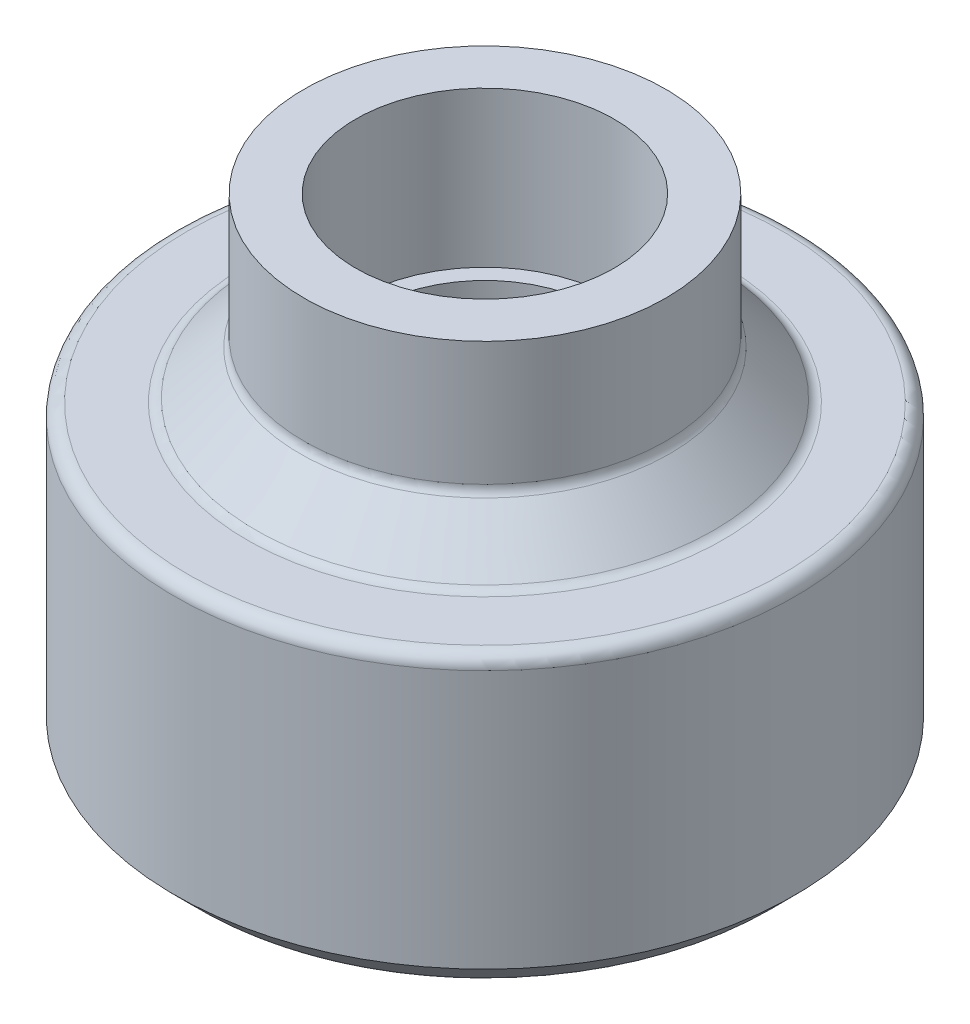
SolidWorks part; units mm, degrees
material "Inconel 718"
ref_plane "Front Plane" through (0, 0, 0) normal (0, 0, 1) x (1, 0, 0)
ref_plane "Top Plane" through (0, 0, 0) normal (0, 1, 0) x (1, 0, 0)
ref_plane "Right Plane" through (0, 0, 0) normal (1, 0, 0) x (0, 0, -1)
sketch "Sketch1" plane through (0, 0, 0) normal (0, 0, 1) x (1, 0, 0)
  line L0 (0, -1033.02) -> (0, -16.51) construction
  line L1 (0, 0) -> (6.35, 0)
  line L2 (6.35, 0) -> (6.35, 7.62)
  line L3 (6.35, 7.62) -> (8.89, 7.62)
  line L4 (8.89, 7.62) -> (8.89, 1.27)
  line L5 (8.89, 1.27) -> (11.43, -1.27)
  line L6 (15.24, -1.27) -> (15.24, -16.51)
  line L8 (11.43, -1.27) -> (15.24, -1.27)
  line L9 (0, -5.8371) -> (0, 0)
  line L10 (15.24, -16.51) -> (13.97, -16.51)
  line L11 (13.97, -16.51) -> (0, -5.8371)
  line L12 (0, -5.8371) -> (0, 43.942) construction
  dimension "D8" = 3.81
  dimension "D9" = 1.27
  dimension "D1" = 6.35
  dimension "D2" = 7.62
  dimension "D3" = 2.54
  dimension "D4" = 15.24
  dimension "D6" = 6.35
  dimension "D7" = 135
  dimension "D13" = 15.24
revolve "Revolve1" add sketch "Sketch1" angle 360 about L0
cosmetic thread "Cosmetic Thread1" parameters "D1"=6.35, "D2"=14.2875
ref_plane "Plane2" through (-15.24, 0, 0) normal (-1, 0, 0) x (0, 0, 1)
chamfer "Chamfer1" distance 1.905 angle 45 1 edges at (15.24, -16.51, 0)
fillet "Fillet1" radius 0.635 4 edges at (-13.61, -16.235, 0) (8.89, 1.27, 0) (15.24, -1.27, 0) (11.43, -1.27, 0)
hole_wizard "7/16 (0.4375) Dowel Hole1" positions "Sketch4" profile "Sketch5" hole size "7/16" standard "ANSI Inch"
sketch "Sketch4" plane through (0, 0, 0) normal (0, 1, 0) x (1, 0, 0)
  point P0 (0, 0)
sketch "Sketch5" plane through (0, 0, 0) normal (1, 0, 0) x (0, 0, 1)
  line L0 (0, 0) -> (0, 15.2765)
  line L1 (0, 15.2765) -> (5.5562, 11.938)
  line L2 (5.5562, 11.938) -> (5.5562, 0)
  line L5 (5.5562, 0) -> (0, 0)
  line L10 (0, 15.2765) -> (-5.5563, 11.938) construction
  line L11 (0, -6.35) -> (0, 107.95) construction
  dimension "Hole Dia." = 11.1125
  dimension "Hole Depth" = 11.938
  dimension "Drill Angle" = 118
